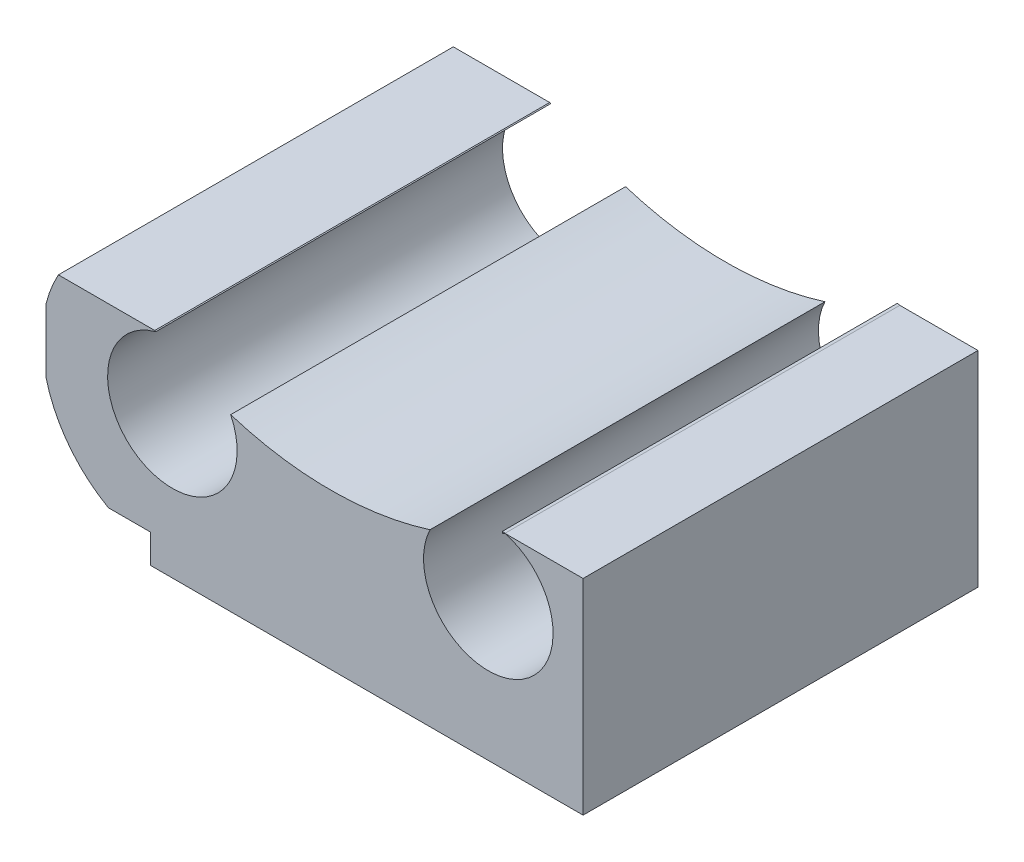
SolidWorks part; units mm, degrees
material "PET"
ref_plane "Front Plane" through (0, 0, 0) normal (0, 0, 1) x (1, 0, 0)
ref_plane "Top Plane" through (0, 0, 0) normal (0, 1, 0) x (1, 0, 0)
ref_plane "Right Plane" through (0, 0, 0) normal (1, 0, 0) x (0, 0, -1)
sketch "Sketch1" plane through (0, 0, 0) normal (0, 0, 1) x (1, 0, 0)
  line L0 (-10, -21.8174) -> (10, -21.8174) construction
  line L1 (22.2174, -11.8174) -> (-7.7826, -25.5679) construction
  line L2 (10, -21.8174) -> (0, 0) construction
  line L3 (0, 0) -> (8.3333, -18.1812) construction
  circle A0 centre (0, 0) radius 20 construction
  circle A1 centre (-10, -21.8174) radius 4 construction
  circle A2 centre (10, -21.8174) radius 4 construction
  dimension "D1" = 40
  dimension "D2" = 8
  dimension "D3" = 8
  dimension "D5" = 30
  dimension "D4" = 20
  dimension "D6" = 10
  dimension "D7" = 24.624
  dimension "D8" = 1.6667
  dimension "D9" = 3.6362
sketch "Sketch2" plane through (0, 0, 0) normal (1, 0, 0) x (0, 0, -1)
  line L1 (-40, -26.8174) -> (-40, -17.8174)
  line L2 (-40, -17.8174) -> (40, -17.8174)
  line L3 (40, -17.8174) -> (40, -26.8174)
  line L4 (0, -30) -> (40, -26.8174)
  line L5 (0, -30) -> (0, -17.8174) construction
  line L6 (0, -30) -> (-40, -26.8174)
  dimension "D1" = 30
  dimension "D2" = 80
  dimension "D3" = 9
  dimension "D4" = 12.1826
extrude "Boss-Extrude1" add sketch "Sketch2" along normal mid plane 36
sketch "Sketch3" plane through (0, 0, 40) normal (0, 0, 1) x (1, 0, 0)
  line L0 (-18, -17.8174) -> (-17.2154, -17.8174)
  line L1 (18, -17.8174) -> (-18, -17.8174) construction
  line L2 (-18, -17.8174) -> (-18, -30.0674)
  line L3 (-18, -30.0674) -> (18, -30.0674)
  line L4 (18, -30.0674) -> (18, -17.8174)
  line L5 (18, -17.8174) -> (17.2154, -17.8174)
  circle A0 centre (-10, -21.8174) radius 4.1
  circle A1 centre (10, -21.8174) radius 4.1
  circle A2 centre (0, 0) radius 20.5
  circle A3 centre (-10, -21.8174) radius 8.25
  circle A4 centre (10, -21.8174) radius 8.25
  line M4 (-18, -17.8174) -> (-18, -26.8174)
  line M5 (-18, -26.8174) -> (18, -26.8174)
  line M6 (18, -26.8174) -> (18, -17.8174)
  line M7 (18, -17.8174) -> (-18, -17.8174)
  dimension "D1" = 8.2
  dimension "D2" = 41
  dimension "D3" = 16.5
  dimension "D4" = 12.25
extrude "Cut-Extrude3" cut sketch "Sketch3" against normal through all contours A3 L2 L3 M5 | A3 M4 M5 | A3 M7 M4 | A4 L3 L4 M5 | A2 A1 M7 | A1 A2 M7 | A2 A0 M7 | A2 A0 M7 | A4 M5 M6 | A2 A3 A0 M7 | A4 A3 A2 M7 | A4 A2 A1 M7 region at (-17.7537, -18.4324, 40) region at (-10.0485, -21.927, 40) region at (-17.5583, -25.9207, 40) region at (0, -19.0539, 40) region at (-4.682, -18.8755, 40) region at (-8.3605, -18.4328, 40) region at (-15.9558, -28.845, 40) region at (4.682, -18.8755, 40) region at (8.3605, -18.4328, 40) region at (15.9558, -28.845, 40) region at (10.0485, -21.927, 40) region at (17.5583, -25.9207, 40)
ref_plane "Plane1" through (26, 0, 0) normal (1, 0, 0) x (0, 0, -1)
sketch "Sketch5" plane through (26, 0, 0) normal (1, 0, 0) x (0, 0, -1)
  line L0 (0, 0) -> (0, 42.3332) construction
  line L1 (12.5, 12.5) -> (-12.5, 12.5)
  line L2 (-12.5, 12.5) -> (-12.5, 0)
  line L5 (12.5, 12.5) -> (12.5, 0)
  line L6 (-12.5, 0) -> (12.5, 0) construction
  line L7 (-12.5, 0) -> (-40, -17.8174)
  line L8 (40, -17.8174) -> (-40, -17.8174) construction
  line L9 (12.5, 0) -> (40, -17.8174)
  line L10 (40, -17.8174) -> (40, -23.833)
  line L12 (40, -23.833) -> (-40, -23.833)
  line L13 (-40, -23.833) -> (-40, -17.8174)
  circle A0 centre (0, 0) radius 10.5 construction
  point P13 (0, 12.5)
  dimension "D1" = 21
  dimension "D2" = 12.5
  dimension "D3" = 12.5
extrude "Boss-Extrude2" add sketch "Sketch5" against normal up to vertex (15.1 mm away) up to point (10.9, -17.8174, 40)
sketch "Sketch7" plane through (0, 0, 0) normal (0, 0, 1) x (1, 0, 0)
  circle A0 centre (0, 0) radius 21
  circle A1 centre (10, -21.8174) radius 4.1
  dimension "D1" = 42
  dimension "D2" = 8.2
extrude "Cut-Extrude5" cut sketch "Sketch7" against normal through all both and the other way through all contours A1 A0 | A0 A1 region at (-0.0242, 0.0528, 0) region at (10.1158, -22.0702, 0)
sketch "Sketch11" plane through (0, 0, 0) normal (1, 0, 0) x (0, 0, -1)
  line L0 (-12.5, 12.5) -> (-12.5, -37.5)
  line L2 (12.5, 12.5) -> (12.5, -37.5)
  line L4 (-12.5, 12.5) -> (-57.5, 12.5)
  line L5 (-57.5, 12.5) -> (-57.5, -37.5)
  line L6 (-57.5, -37.5) -> (-12.5, -37.5)
  line L7 (12.5, -37.5) -> (57.5, -37.5)
  line L8 (57.5, -37.5) -> (57.5, 12.5)
  line L9 (57.5, 12.5) -> (12.5, 12.5)
  dimension "D1" = 50
  dimension "D2" = 45
  dimension "D3" = 45
  dimension "D4" = 50
extrude "Cut-Extrude8" cut sketch "Sketch11" against normal mid plane 70
sketch "Sketch12" plane through (0, 0, 12.5) normal (0, 0, 1) x (1, 0, 0)
  line L0 (11.054, -17.8552) -> (26, -17.8552)
  line L1 (26, -13.75) -> (26, 13.75) construction
  line L2 (26, -17.8552) -> (26, 12.5)
  line L3 (16.8745, 12.5) -> (26, 12.5) construction
  line L4 (11.054, -17.8552) -> (11.054, 12.5)
  line L5 (11.054, 12.5) -> (26, 12.5)
extrude "Cut-Extrude9" cut sketch "Sketch12" against normal blind 70
sketch "Sketch13" plane through (0, -23.833, 0) normal (0, -1, 0) x (1, 0, 0)
  line L0 (26, 12.5) -> (13.6, 12.5)
  line L1 (13.6, 12.5) -> (13.6, -12.5)
  line L2 (13.6, -12.5) -> (26, -12.5)
  line L3 (26, -12.5) -> (26, 12.5)
  dimension "D1" = 12.4
extrude "Boss-Extrude3" add sketch "Sketch13" along normal blind 7
sketch "Sketch14" plane through (0, 0, 12.5) normal (0, 0, 1) x (1, 0, 0)
  line L0 (16, -30.833) -> (16, -17.8552)
  line L1 (26, -30.833) -> (13.6, -30.833) construction
  line L2 (11.054, -17.8552) -> (26, -17.8552) construction
  line L3 (16, -17.8552) -> (26, -17.8552)
  line L4 (26, -13.75) -> (26, 13.75) construction
  line L5 (26, -17.8552) -> (26, -30.833)
  line L6 (26, -30.833) -> (16, -30.833)
  dimension "D1" = 10
extrude "Cut-Extrude10" cut sketch "Sketch14" against normal blind 40
sketch "Sketch15" plane through (13.6, 0, 0) normal (-1, 0, 0) x (0, 0, 1)
  line L0 (12.5, -30.833) -> (-12.5, -30.833)
  line L1 (-12.5, -30.833) -> (-12.5, -29.0054)
  line L2 (-12.5, -29.0054) -> (12.5, -29.0054)
  line L3 (12.5, -29.0054) -> (12.5, -30.833)
extrude "Boss-Extrude4" add sketch "Sketch15" along normal blind 25
sketch "Sketch17" plane through (0, -30.833, 0) normal (0, -1, 0) x (-1, 0, 0)
  line L0 (0, 12.5) -> (0, -12.5) construction
  line L1 (11.4, 12.5) -> (-16, 12.5) construction
  line L2 (-16, -12.5) -> (11.4, -12.5) construction
  line L3 (11, -12.5) -> (11, 12.5)
  line L4 (11, 12.5) -> (6, 12.5)
  line L5 (6, 12.5) -> (6, -12.5)
  line L6 (6, -12.5) -> (11, -12.5)
  dimension "D1" = 5
  dimension "D2" = 6
extrude "Boss-Extrude5" add sketch "Sketch17" along normal blind 5
sketch "Sketch18" plane through (-6, 0, 0) normal (1, 0, 0) x (0, 0, -1)
  line L0 (12.5, -30.833) -> (6.5, -35.833)
  line L1 (12.5, -35.833) -> (-12.5, -35.833) construction
  line L2 (6.5, -35.833) -> (12.5, -35.833)
  line L3 (12.5, -35.833) -> (12.5, -30.833)
  line L4 (0, -35.833) -> (0, -30.833) construction
  line L5 (12.5, -30.833) -> (-12.5, -30.833) construction
  line L6 (-6.5, -35.833) -> (-12.5, -35.833)
  line L7 (-12.5, -35.833) -> (-12.5, -30.833)
  line L8 (-12.5, -30.833) -> (-6.5, -35.833)
  dimension "D1" = 6
extrude "Cut-Extrude11" cut sketch "Sketch18" against normal blind 15
sketch "Sketch19" plane through (-6, 0, 0) normal (1, 0, 0) x (0, 0, -1)
  line L0 (0, -35.833) -> (0, -30.833) construction
  line L1 (6.5, -35.833) -> (-6.5, -35.833) construction
  line L2 (12.5, -30.833) -> (-12.5, -30.833) construction
  line L3 (9.5, -33.333) -> (-9.5, -33.333) construction
  line L4 (-6.5, -35.833) -> (-12.5, -30.833) construction
  line L5 (12.5, -30.833) -> (6.5, -35.833) construction
  circle A0 centre (-7.5, -33.333) radius 0.9
  circle A1 centre (-3.75, -33.333) radius 0.9
  circle A2 centre (0, -33.333) radius 0.9
  circle A3 centre (3.75, -33.333) radius 0.9
  circle A4 centre (7.5, -33.333) radius 0.9
  dimension "D1" = 1.8
  dimension "D2" = 2
  dimension "D4" = 2
  dimension "D3" = 5
extrude "Cut-Extrude12" cut sketch "Sketch19" against normal blind 15
